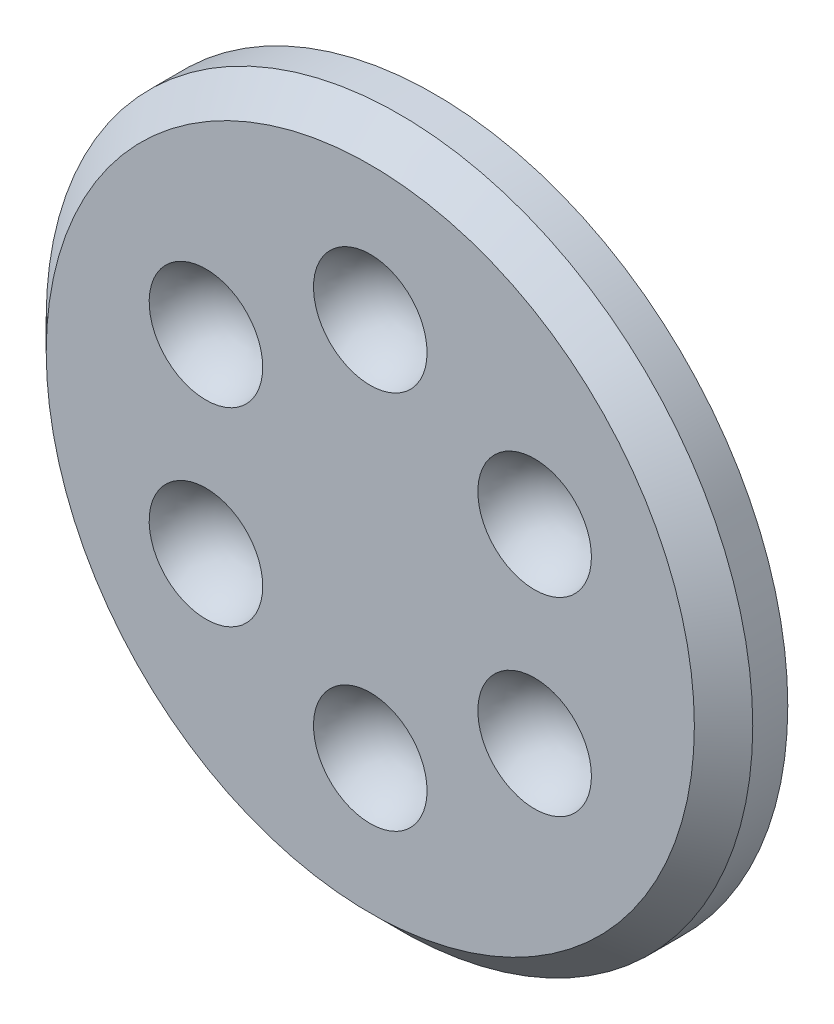
SolidWorks part; units mm, degrees
material "Copper"
ref_plane "Front Plane" through (0, 0, 0) normal (0, 0, 1) x (1, 0, 0)
ref_plane "Top Plane" through (0, 0, 0) normal (0, 1, 0) x (1, 0, 0)
ref_plane "Right Plane" through (0, 0, 0) normal (1, 0, 0) x (0, 0, -1)
sketch "Sketch1" plane through (0, 0, 0) normal (0, 0, 1) x (1, 0, 0)
  circle A0 centre (0, 0) radius 15.367
  dimension "D1" = 30.734
extrude "Boss-Extrude1" add sketch "Sketch1" along normal blind 2.794
sketch "Sketch2" plane through (0, 0, 2.794) normal (0, 0, 1) x (1, 0, 0)
  line L0 (0, 0) -> (0, 8.255)
  line L1 (0, 0) -> (7.149, 4.1275)
  line L2 (0, 0) -> (7.149, -4.1275)
  line L3 (0, 0) -> (0, -8.255)
  line L4 (0, 0) -> (-7.149, -4.1275)
  line L5 (0, 0) -> (-7.149, 4.1275)
  point P10 (0, 0)
  dimension "D1" = 8.255
  dimension "D2" = 6
ref_plane "Plane1" through (0, 0, 0) normal (1, 0, 0) x (0, 0, -1)
sketch "Sketch3" plane through (0, 0, 0) normal (1, 0, 0) x (0, 0, -1)
  line L0 (-2.794, 8.255) -> (-3.556, 8.255) construction
  line L1 (-2.794, 0) -> (-2.794, 8.255) construction
  line L2 (-2.794, 15.367) -> (-2.794, -15.367) construction
  line L3 (-6.1405, 8.255) -> (-0.9716, 8.255) construction
  line L4 (-6.1405, 8.255) -> (-0.9716, 8.255)
  arc A0 (-0.9716, 8.255) -> (-6.1405, 8.255) centre (-3.556, 8.255) ccw
  dimension "D2" = 5.1689
  dimension "D1" = 0.762
revolve "Cut-Revolve1" cut sketch "Sketch3" angle 360 about L4
ref_axis "Axis1" through (0, 0, 2.794) along (0, 0, -1)
pattern_circular "CirPattern1" count 6 over 360 about axis through (0, 0, 2.794) along (0, 0, -1) of "Cut-Revolve1"
chamfer "Chamfer1" distance 1.27 angle 45 1 edges at (15.367, 0, 2.794)
sketch "Sketch4" plane through (0, 0, 2.794) normal (0, 0, 1) x (1, 0, 0)
  line L0 (-14.097, 0) -> (14.097, 0)
  circle A0 centre (0, 0) radius 14.097 construction
